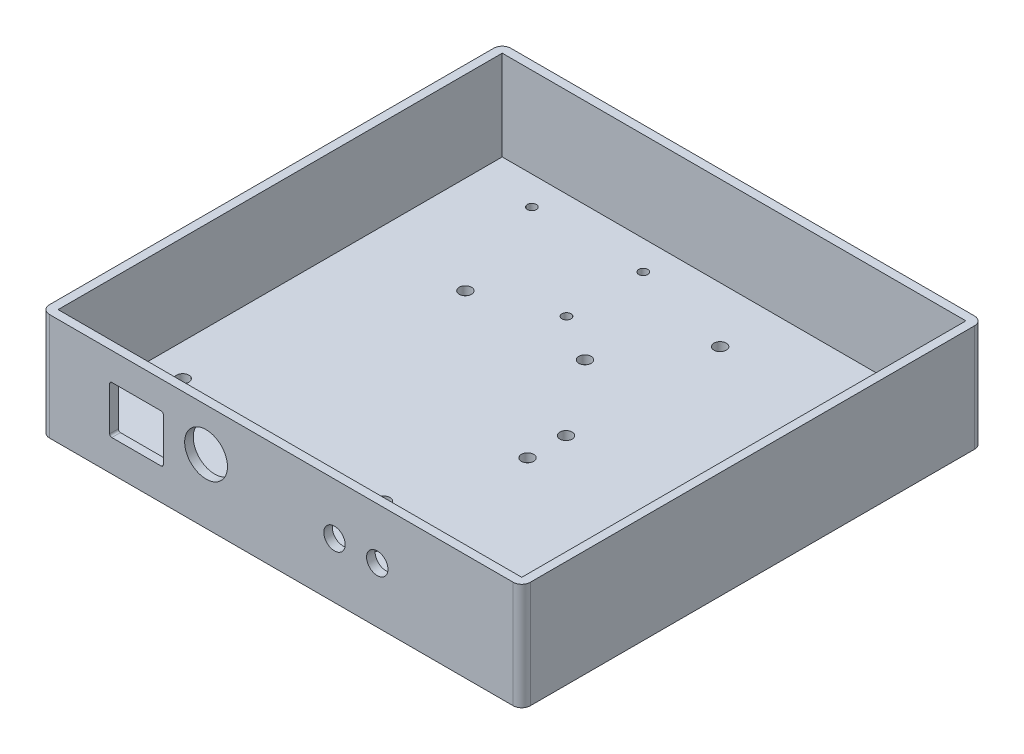
SolidWorks part; units mm, degrees
ref_plane "Front Plane" through (0, 0, 0) normal (0, 0, 1) x (1, 0, 0)
ref_plane "Top Plane" through (0, 0, 0) normal (0, 1, 0) x (1, 0, 0)
ref_plane "Right Plane" through (0, 0, 0) normal (1, 0, 0) x (0, 0, -1)
sketch "Sketch1" plane through (0, 878.6284, 0) normal (0, 1, 0) x (1, 0, 0)
  line L0 (666.5112, -1261.621) -> (666.5112, -1327.661) construction
  line L1 (661.5112, -1230.231) -> (769.8512, -1230.231)
  line L2 (661.5112, -1230.231) -> (661.5112, -1334.011)
  line L3 (661.5112, -1334.011) -> (769.8512, -1334.011)
  line L4 (769.8512, -1230.231) -> (769.8512, -1334.011)
  line L5 (666.5112, -1261.621) -> (666.5112, -1327.661)
  line L6 (666.5112, -1327.661) -> (719.8512, -1327.661) construction
  line L7 (666.5112, -1327.661) -> (719.8512, -1327.661)
  line L8 (764.8512, -1327.661) -> (764.8512, -1284.661) construction
  line L9 (708.6548, -1235.231) -> (672.3548, -1235.231) construction
  line L10 (687.3912, -1334.011) -> (676.2712, -1334.011) construction
  dimension "D2" = 5
  dimension "D1" = 5
  dimension "D3" = 5
extrude "Boss-Extrude1" add sketch "Sketch1" against normal blind 4 contours L3 L4 L1 L2
sketch "Sketch2" plane through (0, 874.6284, 0) normal (0, 1, 0) x (1, 0, 0)
  line L1 (661.5112, -1230.231) -> (659.5112, -1230.231)
  line L2 (661.5112, -1230.231) -> (661.5112, -1334.011)
  line L3 (661.5112, -1334.011) -> (659.5112, -1334.011)
  line L4 (661.5112, -1230.231) -> (661.5112, -1334.011)
  line L5 (661.5112, -1334.011) -> (769.8512, -1334.011)
  line L6 (769.8512, -1334.011) -> (769.8512, -1230.231)
  line L7 (769.8512, -1230.231) -> (661.5112, -1230.231)
  line L8 (661.5112, -1230.231) -> (661.5112, -1334.011)
  line L9 (661.5112, -1334.011) -> (769.8512, -1334.011)
  line L10 (769.8512, -1334.011) -> (769.8512, -1230.231)
  line L11 (769.8512, -1230.231) -> (661.5112, -1230.231)
  line L12 (659.5112, -1230.231) -> (659.5112, -1334.011)
  line L13 (659.5112, -1230.231) -> (769.8512, -1230.231)
  line L14 (659.5112, -1230.231) -> (659.5112, -1228.231)
  line L15 (659.5112, -1228.231) -> (769.8512, -1228.231)
  line L16 (769.8512, -1230.231) -> (769.8512, -1228.231)
  line L17 (769.8512, -1228.231) -> (771.8512, -1228.231)
  line L18 (769.8512, -1228.231) -> (769.8512, -1334.011)
  line L19 (769.8512, -1334.011) -> (771.8512, -1334.011)
  line L20 (771.8512, -1228.231) -> (771.8512, -1334.011)
  line L21 (659.5112, -1334.011) -> (771.8512, -1334.011)
  line L22 (659.5112, -1334.011) -> (659.5112, -1336.011)
  line L23 (659.5112, -1336.011) -> (771.8512, -1336.011)
  line L24 (771.8512, -1334.011) -> (771.8512, -1336.011)
  dimension "D2" = 2
extrude "Boss-Extrude2" add sketch "Sketch2" along normal blind 25 separate body contours L16 L15 L14 L1 | L1 L12 L3 | L20 L17 L16 L19 | L24 L19 L3 L22 L23 region at (660.5112, 874.6284, 1282.121) region at (714.6812, 874.6284, 1229.231) region at (715.6812, 874.6284, 1335.011) region at (770.8512, 874.6284, 1281.121)
sketch "Sketch4" plane through (0, 0, 1336.011) normal (0, 0, 1) x (1, 0, 0)
  line L0 (687.5912, 893.1684) -> (676.0712, 893.1684)
  line L1 (675.5712, 892.6684) -> (675.5712, 882.5184)
  line L2 (676.0712, 882.0184) -> (687.5912, 882.0184)
  line L3 (688.0912, 882.5184) -> (688.0912, 892.6684)
  line L4 (687.3912, 892.4684) -> (676.2712, 892.4684)
  line L5 (676.2712, 892.4684) -> (676.2712, 882.7184)
  line L6 (676.2712, 882.7184) -> (687.3912, 882.7184)
  line L7 (687.3912, 882.7184) -> (687.3912, 892.4684)
  line L8 (687.3912, 892.4684) -> (676.2712, 892.4684)
  line L9 (676.2712, 892.4684) -> (676.2712, 882.7184)
  line L10 (676.2712, 882.7184) -> (687.3912, 882.7184)
  line L11 (687.3912, 882.7184) -> (687.3912, 892.4684)
  line L12 (675.5712, 882.0184) -> (688.0912, 882.0184) construction
  line L13 (675.5712, 893.1684) -> (675.5712, 882.0184) construction
  line L14 (688.0912, 882.0184) -> (688.0912, 893.1684) construction
  line L15 (688.0912, 893.1684) -> (675.5712, 893.1684) construction
  arc A0 (676.0712, 882.0184) -> (675.5712, 882.5184) centre (676.0712, 882.5184) cw
  arc A1 (688.0912, 882.5184) -> (687.5912, 882.0184) centre (687.5912, 882.5184) cw
  arc A2 (688.0912, 892.6684) -> (687.5912, 893.1684) centre (687.5912, 892.6684) ccw
  arc A3 (676.0712, 893.1684) -> (675.5712, 892.6684) centre (676.0712, 892.6684) ccw
  dimension "D2" = 0.7
extrude "Cut-Extrude1" cut sketch "Sketch4" against normal up to surface (2 mm away) contours L10 L11 L8 L9 | L0 A3 L1 A0 L2 A1 L3 A2 L11 L10 L9 L8 region at (687.8262, 892.9034, 1336.011) region at (681.8312, 887.5934, 1336.011) up to face at (715.6812, 887.1284, 1334.011)
fillet "Fillet1" radius 2 4 edges at (659.5112, 887.1284, 1336.011) (659.5112, 887.1284, 1228.231) (771.8512, 887.1284, 1228.231) (771.8512, 887.1284, 1336.011)
sketch "Sketch5" plane through (0, 878.6284, 0) normal (0, 1, 0) x (1, 0, 0)
  circle A0 centre (761.3512, -1243.161) radius 1.75 construction
  circle A1 centre (761.3512, -1279.161) radius 1.75 construction
  circle A2 centre (725.3512, -1279.161) radius 1.75 construction
  circle A3 centre (725.3512, -1243.161) radius 1.75 construction
  circle A4 centre (761.3512, -1324.161) radius 1.75 construction
  circle A5 centre (761.3512, -1288.161) radius 1.75 construction
  circle A6 centre (725.3512, -1288.161) radius 1.75 construction
  circle A7 centre (725.3512, -1324.161) radius 1.75 construction
  circle A8 centre (669.0512, -1312.421) radius 1.5875 construction
  circle A9 centre (717.3112, -1313.691) radius 1.5875 construction
  circle A10 centre (675.1048, -1236.911) radius 1.05 construction
  circle A11 centre (701.2648, -1237.031) radius 1.05 construction
  circle A12 centre (701.2648, -1254.971) radius 1.05 construction
  circle A13 centre (712.2312, -1261.621) radius 1.5875 construction
  circle A14 centre (684.2912, -1261.621) radius 1.5875 construction
  circle A15 centre (761.3512, -1243.161) radius 1.75
  circle A16 centre (761.3512, -1279.161) radius 1.75
  circle A17 centre (725.3512, -1279.161) radius 1.75
  circle A18 centre (725.3512, -1243.161) radius 1.75
  circle A19 centre (761.3512, -1324.161) radius 1.75
  circle A20 centre (761.3512, -1288.161) radius 1.75
  circle A21 centre (725.3512, -1288.161) radius 1.75
  circle A22 centre (725.3512, -1324.161) radius 1.75
  circle A23 centre (669.0512, -1312.421) radius 1.5875
  circle A24 centre (717.3112, -1313.691) radius 1.5875
  circle A25 centre (675.1048, -1236.911) radius 1.05
  circle A26 centre (701.2648, -1237.031) radius 1.05
  circle A27 centre (701.2648, -1254.971) radius 1.05
  circle A28 centre (712.2312, -1261.621) radius 1.5875
  circle A29 centre (684.2912, -1261.621) radius 1.5875
  circle A30 centre (684.2912, -1261.621) radius 1.4375
  circle A31 centre (712.2312, -1261.621) radius 1.4375
  circle A32 centre (725.3512, -1279.161) radius 1.4375
  circle A33 centre (725.3512, -1288.161) radius 1.4375
  circle A34 centre (761.3512, -1279.161) radius 1.4375
  circle A35 centre (725.3512, -1243.161) radius 1.4375
  circle A36 centre (761.3512, -1243.161) radius 1.4375
  circle A37 centre (761.3512, -1288.161) radius 1.4375
  circle A38 centre (717.3112, -1313.691) radius 1.4375
  circle A39 centre (725.3512, -1324.161) radius 1.4375
  circle A40 centre (761.3512, -1324.161) radius 1.4375
  circle A41 centre (669.0512, -1312.421) radius 1.4375
  dimension "D1" = 0.15
extrude "Cut-Extrude2" cut sketch "Sketch5" against normal blind 2 contours A30 | A25 | A26 | A27 | A31 | A35 | A36 | A32 | A34 | A37 | A33 | A40 | A39 | A38 | A41 region at (675.1048, 878.6284, 1236.911) region at (701.2648, 878.6284, 1237.031) region at (701.2648, 878.6284, 1254.971) region at (684.2912, 878.6284, 1261.621) region at (712.2312, 878.6284, 1261.621) region at (725.3512, 878.6284, 1279.161) region at (725.3512, 878.6284, 1288.161) region at (761.3512, 878.6284, 1279.161) region at (725.3512, 878.6284, 1243.161) region at (761.3512, 878.6284, 1243.161) region at (761.3512, 878.6284, 1288.161) region at (717.3112, 878.6284, 1313.691) region at (725.3512, 878.6284, 1324.161) region at (761.3512, 878.6284, 1324.161) region at (669.0512, 878.6284, 1312.421)
sketch "Sketch6" plane through (0, 0, 1336.011) normal (0, 0, 1) x (1, 0, 0)
  line L0 (688.0912, 882.5184) -> (688.0912, 892.6684) construction
  line L1 (688.0912, 882.5184) -> (688.0912, 892.6684)
  line L3 (728.0912, 887.5934) -> (738.0912, 887.5934)
  line L4 (661.5112, 874.6284) -> (769.8512, 874.6284) construction
  circle A0 centre (698.0912, 889.6284) radius 5
  circle A1 centre (728.0912, 887.5934) radius 2.5
  circle A2 centre (738.0912, 887.5934) radius 2.5
  point P2 (698.6947, 889.45)
  point P9 (712.3925, 887.5934)
  point P10 (730.2754, 887.5934)
  point P11 (0, 0)
  point P14 (0, 0)
  point P15 (730.0718, 888.5477)
  point P16 (688.0912, 887.5934)
  point P17 (730.1467, 887.5934)
  dimension "D3" = 5
  dimension "D1" = 10
  dimension "D5" = 10
  dimension "D2" = 10
  dimension "D6" = 15
  dimension "D4" = 40
extrude "Cut-Extrude3" cut sketch "Sketch6" against normal up to surface (2 mm away) contours A0 | A0 | L3 A1 | A1 L3 | A2 region at (738.0912, 890.0227, 1336.011) region at (725.662, 887.5934, 1336.011) region at (698.0912, 889.6284, 1336.011) up to face at (681.8312, 887.5934, 1334.011)
equation "\"D2\"=110"
equation "\"C\"=5"
equation "\"D2@Sketch1\"=\"C\""
equation "\"D1\"=100"
equation "\"T\"= 2"
equation "\"BT\"=4"
equation "\"D1@Boss-Extrude1\"=\"BT\""
equation "\"D1@Sketch1\"=\"C\""
equation "\"D3@Sketch1\"=\"C\""
equation "\"D2@Sketch2\"=\"T\""
equation "\"H\"= 25"
equation "\"D1@Boss-Extrude2\"=\"H\""
equation "\"CS\"=0.7"
equation "\"D2@Sketch4\"=\"CS\""
equation "\"F\"=0.5"
equation "\"D3@Sketch4\"=\"F\""
equation "\"F2\"=2"
equation "\"D1@Fillet1\"=\"F2\""
equation "\"D\"=2"
equation "\"D1@Cut-Extrude2\"=\"D\""
equation "\"HOLED\"=10"
equation "\"D1@Sketch6\"=\"HOLED\""
equation "\"CSS\"=0.15"
equation "\"D1@Sketch5\"=\"CSS\""
equation "\"WIREH\"=5"
equation "\"D3@Sketch6\"=\"WIREH\""
